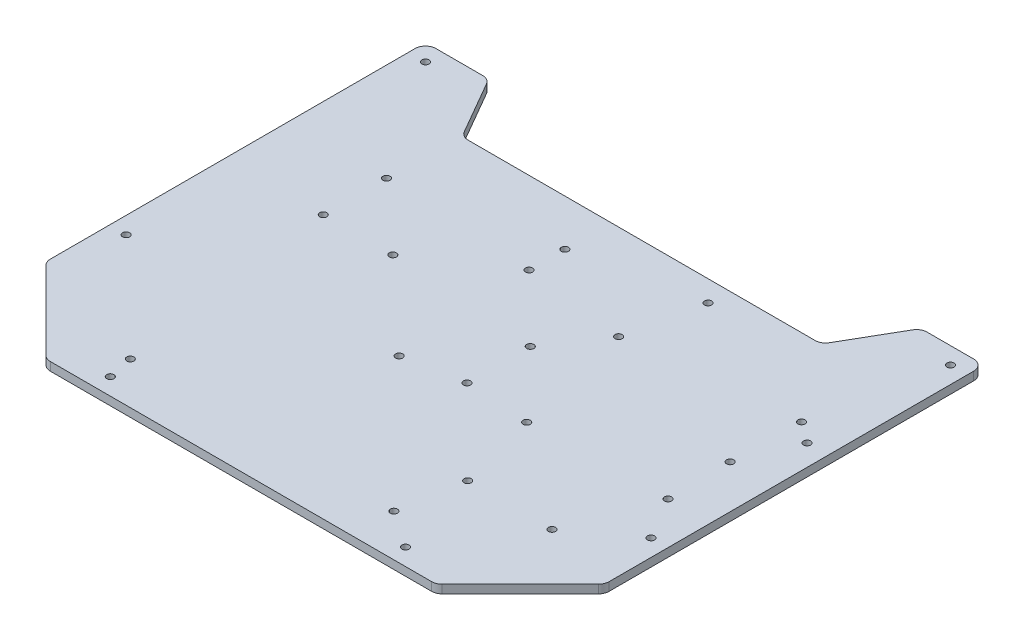
SolidWorks part; units mm, degrees
material "Acier non allié"
ref_plane "Front" through (0, 0, 0) normal (0, 0, 1) x (1, 0, 0)
ref_plane "Top" through (0, 0, 0) normal (0, 1, 0) x (1, 0, 0)
ref_plane "Right" through (0, 0, 0) normal (1, 0, 0) x (0, 0, -1)
sketch "Main scetch" plane through (0, 0, 0) normal (0, 1, 0) x (1, 0, 0)
  line L1 (0, 0) -> (132.5, 0) construction
  line L2 (0, 0) -> (0, 220) construction
  line L3 (0, 220) -> (132.5, 220) construction
  line L4 (132.5, 0) -> (132.5, 220) construction
  line L13 (-92.5, 0) -> (92.5, 0)
  line L14 (92.5, 0) -> (132.5, 40)
  line L15 (132.5, 40) -> (132.5, 220)
  line L16 (132.5, 220) -> (102.5, 220)
  line L17 (102.5, 220) -> (85.1795, 190)
  line L18 (85.1795, 190) -> (-85.1795, 190)
  line L19 (-102.5, 220) -> (-85.1795, 190)
  line L20 (-132.5, 220) -> (-102.5, 220)
  line L21 (-132.5, 40) -> (-132.5, 220)
  line L22 (-92.5, 0) -> (-132.5, 40)
  point P11 (0, 190)
  dimension "132.5" = 132.5
  dimension "D2" = 220
  dimension "D1" = 40
  dimension "D3" = 40
  dimension "D4" = 30
  dimension "D5" = 60
  dimension "D6" = 30
extrude "Main extrusion" add sketch "Main scetch" along normal blind 4
fillet "Congé1" radius 5 10 edges at (-132.5, 2, -40) (-92.5, 2, 0) (92.5, 2, 0) (132.5, 2, -40) (132.5, 2, -220) (102.5, 2, -220) (85.1795, 2, -190) (-85.1795, 2, -190) (-102.5, 2, -220) (-132.5, 2, -220)
sketch "Esquisse1" plane through (0, 4, 0) normal (0, 1, 0) x (1, 0, 0)
  line L0 (0, 0) -> (0, 218.5516) construction
  line L1 (132.5, 42.0711) -> (132.5, 215) construction
  line L2 (127.5, 220) -> (105.3868, 220) construction
  line L3 (-90.4289, 0) -> (90.4289, 0) construction
  circle A0 centre (70, 8) radius 1
  circle A1 centre (124.5, 70) radius 1
  circle A2 centre (124.5, 212) radius 1
  circle A3 centre (-124.5, 212) radius 1
  circle A4 centre (-124.5, 70) radius 1
  circle A5 centre (-70, 8) radius 1
  dimension "D1" = 2
  dimension "D2" = 2
  dimension "D3" = 2
  dimension "D4" = 8
  dimension "D5" = 8
  dimension "D6" = 8
  dimension "D7" = 8
  dimension "D8" = 70
  dimension "D9" = 70
extrude "Enlèv. mat.-Extru.1" cut sketch "Esquisse1" against normal through all
hole_wizard "Dégagement M31" positions "Esquisse2" profile "Esquisse3" hole size "M3" standard "ISO" end condition through all
sketch "Esquisse2" plane through (0, 4, 0) normal (0, 1, 0) x (1, 0, 0)
  point P0 (-124.5, 212)
  point P3 (-124.5, 70)
  point P6 (-70, 8)
  point P9 (70, 8)
  point P12 (124.5, 70)
  point P15 (124.5, 212)
sketch "Esquisse3" plane through (-124.5, 4, -212) normal (1, 0, 0) x (0, 0, 1)
  line L0 (0, 0) -> (0, 4)
  line L1 (0, 4) -> (1.7, 4)
  line L2 (1.7, 4) -> (1.7, 0)
  line L5 (1.7, 0) -> (0, 0)
  line L11 (0, -6.35) -> (0, 107.95) construction
  dimension "Diamètre du perçage jusqu'au prochain" = 3.4
  dimension "Profondeur du perçage jusqu'au prochain" = 4
sketch "Esquisse4" plane through (0, 4, 0) normal (0, 1, 0) x (1, 0, 0)
  line L0 (-132.5, 215) -> (-132.5, 42.0711) construction
  line L1 (-105.3868, 220) -> (-127.5, 220) construction
  line L2 (82.2927, 190) -> (-82.2927, 190) construction
  line L3 (132.5, 42.0711) -> (132.5, 215) construction
  line L4 (-90.4289, 0) -> (90.4289, 0) construction
  line L5 (127.5, 220) -> (105.3868, 220) construction
  circle A0 centre (-86, 125) radius 1
  circle A1 centre (-86, 155) radius 1
  circle A2 centre (-53, 125) radius 1
  circle A3 centre (-14.5, 151.1) radius 1
  circle A4 centre (-14.5, 168.1) radius 1
  circle A5 centre (41.5, 180) radius 1
  circle A6 centre (34.12, 145) radius 1
  circle A7 centre (112.5, 153.32) radius 1
  circle A8 centre (122.5, 146) radius 1
  circle A9 centre (112, 120) radius 1
  circle A10 centre (112.5, 90) radius 1
  circle A11 centre (17.2, 120) radius 1
  circle A12 centre (17.2, 90) radius 1
  circle A13 centre (47.5, 88) radius 1
  circle A14 centre (57.5, 50) radius 1
  circle A15 centre (97.5, 50) radius 1
  circle A16 centre (52.5, 20) radius 1
  circle A17 centre (-10, 85) radius 1
  circle A18 centre (-72.5, 20) radius 1
  dimension "D1" = 2
  dimension "D4" = 2
  dimension "D6" = 2
  dimension "D8" = 2
  dimension "D11" = 2
  dimension "D13" = 2
  dimension "D16" = 2
  dimension "D19" = 2
  dimension "D24" = 2
  dimension "D25" = 2
  dimension "D28" = 2
  dimension "D30" = 2
  dimension "D32" = 2
  dimension "D36" = 2
  dimension "D37" = 2
  dimension "D40" = 2
  dimension "D48" = 2
  dimension "D49" = 2
  dimension "D50" = 2
  dimension "D2" = 46.5
  dimension "D3" = 95
  dimension "D5" = 65
  dimension "D7" = 79.5
  dimension "D9" = 38.9
  dimension "D10" = 118
  dimension "D12" = 21.9
  dimension "D14" = 174
  dimension "D15" = 10
  dimension "D17" = 166.62
  dimension "D18" = 45
  dimension "D20" = 20
  dimension "D21" = 66.68
  dimension "D22" = 10
  dimension "D23" = 74
  dimension "D26" = 20.5
  dimension "D27" = 100
  dimension "D29" = 30
  dimension "D31" = 115.3
  dimension "D33" = 115.3
  dimension "D34" = 132
  dimension "D35" = 85
  dimension "D38" = 50
  dimension "D39" = 75
  dimension "D41" = 35
  dimension "D42" = 80
  dimension "D43" = 20
  dimension "D44" = 20
  dimension "D45" = 205
  dimension "D46" = 85
  dimension "D47" = 142.5
extrude "Enlèv. mat.-Extru.2" cut sketch "Esquisse4" against normal through all
hole_wizard "Dégagement M32" positions "Esquisse5" profile "Esquisse6" hole size "M3" standard "ISO" end condition through all
sketch "Esquisse5" plane through (0, 4, 0) normal (0, 1, 0) x (1, 0, 0)
  point P0 (-86, 155)
  point P3 (-86, 125)
  point P6 (-53, 125)
  point P9 (17.2, 120)
  point P12 (-14.5, 151.1)
  point P15 (-14.5, 168.1)
  point P18 (34.12, 145)
  point P21 (41.5, 180)
  point P24 (112.5, 153.32)
  point P27 (122.5, 146)
  point P30 (112, 120)
  point P33 (112.5, 90)
  point P36 (47.5, 88)
  point P39 (17.2, 90)
  point P42 (57.5, 50)
  point P45 (97.5, 50)
  point P48 (-10, 85)
  point P51 (-72.5, 20)
  point P54 (52.5, 20)
sketch "Esquisse6" plane through (-86, 4, -155) normal (1, 0, 0) x (0, 0, 1)
  line L0 (0, 0) -> (0, 4)
  line L1 (0, 4) -> (1.7, 4)
  line L2 (1.7, 4) -> (1.7, 0)
  line L5 (1.7, 0) -> (0, 0)
  line L11 (0, -6.35) -> (0, 107.95) construction
  dimension "Diamètre du perçage jusqu'au prochain" = 3.4
  dimension "Profondeur du perçage jusqu'au prochain" = 4
equation "\"WIDTH\"= 300mm'Total width of the robot"
equation "\"LENGTH\"= 220mm'Total length of the robot"
equation "\"D2@Main scetch\" = \"LENGTH\""
equation "\"CUT_DEPTH\"= 45mm'Depth of the cut on the edges of the plate"
equation "\"Plate_th\"= 3mm'Thickness of the plate"
equation "\"D1\"= \"Plate_th\""
equation "\"D47@Esquisse4\"=(80+205)/2"
